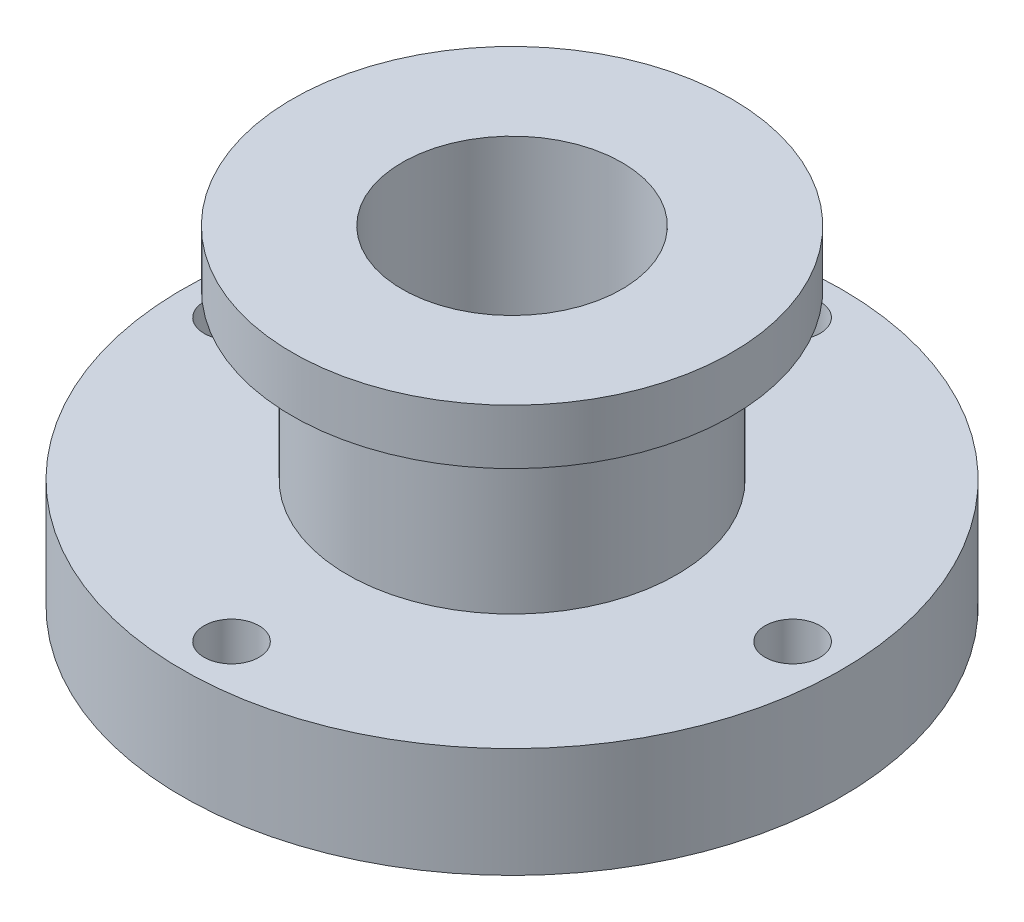
SolidWorks part; units mm, degrees
ref_plane "Front Plane" through (0, 0, 0) normal (0, 0, 1) x (1, 0, 0)
ref_plane "Top Plane" through (0, 0, 0) normal (0, 1, 0) x (1, 0, 0)
ref_plane "Right Plane" through (0, 0, 0) normal (1, 0, 0) x (0, 0, -1)
other "Center of Mass"
sketch "Sketch4" plane through (0, 0, 0) normal (0, 0, 1) x (1, 0, 0)
  line L0 (0, -251.6129) -> (0, -151.6129)
  line L1 (0, -251.6129) -> (300, -251.6129)
  line L2 (300, -251.6129) -> (300, -151.6129)
  line L3 (300, -151.6129) -> (150, -151.6129)
  line L4 (150, -151.6129) -> (150, -1.6129)
  line L5 (150, -1.6129) -> (200, -1.6129)
  line L6 (200, -1.6129) -> (200, 48.3871)
  line L7 (200, 48.3871) -> (152.8226, 48.3871)
  line L8 (152.8226, 48.3871) -> (100, 48.3871)
  line L9 (100, 48.3871) -> (100, -151.6129)
  line L10 (100, -151.6129) -> (0, -151.6129)
  line L11 (0, -251.6129) -> (0, 382.6571) construction
  dimension "D1" = 300
  dimension "D2" = 100
  dimension "D4" = 50
  dimension "D5" = 150
  dimension "D6" = 100
  dimension "D7" = 50
  dimension "D8" = 100
revolve "Revolve2" add sketch "Sketch4" angle 360 about L11
sketch "Sketch5" plane through (0, -151.6129, 0) normal (0, 1, 0) x (1, 0, 0)
  circle A0 centre (0, 255.3655) radius 25
  circle A2 centre (255.3655, 0) radius 25
  circle A3 centre (0, -255.3655) radius 25
  circle A4 centre (-255.3655, 0) radius 25
  dimension "D1" = 4
  dimension "D2" = 50
extrude "Cut-Extrude2" cut sketch "Sketch5" against normal blind 100
ref_axis "Base_Axis" through (0, 48.3871, 0) along (0, -1, 0)
